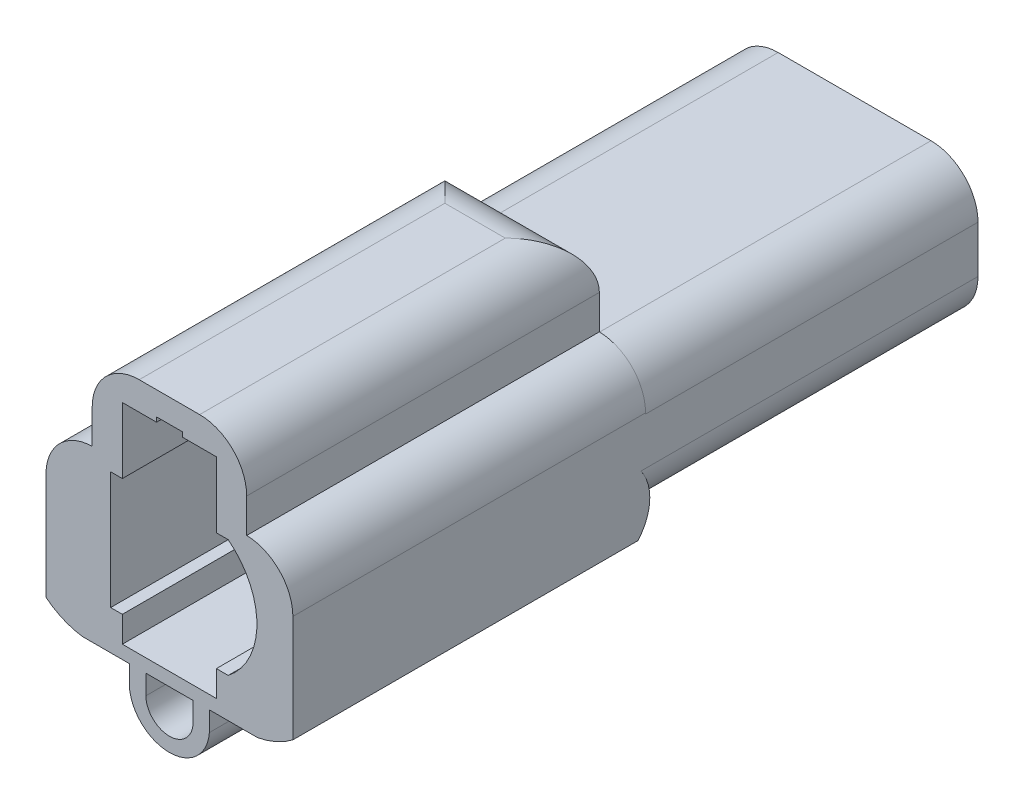
SolidWorks part; units mm, degrees
ref_plane "Front Plane" through (0, 0, 0) normal (0, 0, 1) x (1, 0, 0)
ref_plane "Top Plane" through (0, 0, 0) normal (0, 1, 0) x (1, 0, 0)
ref_plane "Right Plane" through (0, 0, 0) normal (1, 0, 0) x (0, 0, -1)
sketch "Sketch1" plane through (0, 0, 0) normal (0, 0, 1) x (1, 0, 0)
  line L1 (-5.25, 3) -> (5.25, 3)
  line L2 (-5.25, 3) -> (-5.25, -3)
  line L3 (-5.25, -3) -> (5.25, -3)
  line L4 (5.25, 3) -> (5.25, -3)
  line L5 (-5.25, 3) -> (5.25, -3) construction
  line L6 (-5.25, -3) -> (5.25, 3) construction
  point P0 (0, 0)
  dimension "D1" = 10.5
  dimension "D2" = 6
extrude "Boss-Extrude1" add sketch "Sketch1" along normal blind 7.07
sketch "Sketch3" plane through (0, 0, 7.07) normal (0, 0, 1) x (1, 0, 0)
  line L1 (-4.3, 0.9) -> (4.3, 0.9)
  line L2 (-4.3, 0.9) -> (-4.3, -0.9)
  line L3 (-4.3, -0.9) -> (4.3, -0.9)
  line L4 (4.3, 0.9) -> (4.3, -0.9)
  line L5 (-4.3, 0.9) -> (4.3, -0.9) construction
  line L6 (-4.3, -0.9) -> (4.3, 0.9) construction
  point P0 (0, 0)
  dimension "D1" = 8.6
  dimension "D2" = 1.8
extrude "Cut-Extrude2" cut sketch "Sketch3" against normal blind 17
sketch "Sketch4" plane through (0, 0, 7.07) normal (0, 0, 1) x (1, 0, 0)
  line L1 (-5.25, 3) -> (5.25, 3)
  line L2 (-5.25, 3) -> (-5.25, -3)
  line L3 (-5.25, -3) -> (5.25, -3)
  line L4 (5.25, 3) -> (5.25, -3)
  line L5 (-5.25, 3) -> (5.25, -3) construction
  line L6 (-5.25, -3) -> (5.25, 3) construction
  point P0 (0, 0)
extrude "Boss-Extrude2" add sketch "Sketch4" along normal blind 7.07
sketch "Sketch5" plane through (0, 0, 14.14) normal (0, 0, 1) x (1, 0, 0)
  line L1 (-2, 0.9) -> (2, 0.9)
  line L2 (-2, 0.9) -> (-2, -0.9)
  line L3 (-2, -0.9) -> (2, -0.9)
  line L4 (2, 0.9) -> (2, -0.9)
  line L5 (-2, 0.9) -> (2, -0.9) construction
  line L6 (-2, -0.9) -> (2, 0.9) construction
  point P0 (0, 0)
  dimension "D1" = 1.8
  dimension "D2" = 4
extrude "Cut-Extrude3" cut sketch "Sketch5" against normal mid plane 38
fillet "Fillet1" radius 12 1 edges at (2, 0, 7.07)
fillet "Fillet2" radius 12 1 edges at (-2, 0, 7.07)
sketch "Sketch19" plane through (0, 0, 14.14) normal (0, 0, 1) x (1, 0, 0)
  line L1 (-5.25, 5.5) -> (5.25, 5.5)
  line L2 (-5.25, 5.5) -> (-5.25, -5.5)
  line L3 (-5.25, -5.5) -> (5.25, -5.5)
  line L4 (5.25, 5.5) -> (5.25, -5.5)
  line L5 (-5.25, 5.5) -> (5.25, -5.5) construction
  line L6 (-5.25, -5.5) -> (5.25, 5.5) construction
  line L7 (2, 0.9) -> (-2, 0.9)
  line L8 (2, 0.9) -> (2, -0.9)
  line L9 (2, -0.9) -> (-2, -0.9)
  line L10 (-2, 0.9) -> (-2, -0.9)
  line L11 (2, 0.9) -> (-2, -0.9) construction
  line L12 (2, -0.9) -> (-2, 0.9) construction
  point P0 (0, 0)
  point P6 (0, 0)
  dimension "D1" = 11
  dimension "D2" = 10.5
extrude "Boss-Extrude8" add sketch "Sketch19" along normal blind 15
sketch "Sketch20" plane through (0, 0, 29.14) normal (0, 0, 1) x (1, 0, 0)
  line L0 (0, -3.6017) -> (0, -5.5)
  line L1 (-5.25, -5.5) -> (5.25, -5.5) construction
  line L2 (0, -5.5) -> (0, -3.6017)
  line L3 (1.9962, 3.6017) -> (1.9962, 5.3017)
  line L4 (1.9962, -2.5) -> (2.5, -2.5)
  line L5 (-2.5, 2.5) -> (-2.0023, 2.5)
  line L6 (-2.5, 2.5) -> (-2.5, -2.5)
  line L7 (-2.5, -2.5) -> (-2.0023, -2.5)
  line L9 (-2.0023, 2.5) -> (-2.0023, 5.3017)
  line L10 (-2.0023, 5.3017) -> (-0.55, 5.3017)
  line L11 (1.9962, 5.3017) -> (1.9962, 2.5)
  line L12 (0, -3.6017) -> (1.9962, -3.6017)
  line L13 (1.9962, -3.6017) -> (1.9962, -2.5)
  line L15 (-2.0023, -2.5) -> (-2.0023, -3.6017)
  line L16 (-2.0023, -3.6017) -> (0, -3.6017)
  line L18 (1.9962, 3.6017) -> (1.9962, 2.5)
  line L22 (1.9962, 2.5) -> (2.5, 2.5)
  line L23 (5.25, 5.5) -> (-5.25, 5.5) construction
  line L24 (0.55, 5.3017) -> (0.55, 5.5)
  line L25 (-0.55, 5.3017) -> (-0.55, 5.5)
  line L27 (-0.55, 5.5) -> (0.55, 5.5)
  line L28 (0.55, 5.3017) -> (1.9962, 5.3017)
  arc A0 (2.5, 2.5) -> (2.5, -2.5) centre (0.55, 0) cw
  dimension "D1" = 5
  dimension "D2" = 5
extrude "Cut-Extrude8" cut sketch "Sketch20" against normal blind 14.5
sketch "Sketch21" plane through (0, 5.5, 0) normal (0, 1, 0) x (1, 0, 0)
  line L0 (-5.25, -14.14) -> (5.25, -14.14)
  line L1 (5.25, -14.14) -> (5.25, -29.14)
  line L2 (5.25, -29.14) -> (-5.25, -29.14)
  line L3 (-5.25, -29.14) -> (-5.25, -14.14)
extrude "Boss-Extrude9" add sketch "Sketch21" along normal blind 1
sketch "Sketch22" plane through (0, 0, 29.14) normal (0, 0, 1) x (1, 0, 0)
  line L1 (3.2851, 3.0463) -> (5.25, 3.0463)
  line L3 (-5.25, 6.5) -> (-5.25, -5.5) construction
  line L4 (0, 0) -> (0, 2.1098)
  line L5 (0, 2.1098) -> (0, 0)
  line L6 (-1.5897, 0) -> (0, 0)
  line L7 (5.25, 6.5) -> (5.25, 5.5936)
  line L8 (5.25, 6.5) -> (3.7474, 6.5)
  line L11 (-5.25, 5.5936) -> (-5.25, 3.0463)
  line L14 (-5.25, -3.5) -> (-5.25, -5.5)
  line L15 (-3.7014, -4.1682) -> (3.7474, -4.1682)
  line L16 (-5.25, -5.5) -> (5.25, -5.5)
  line L17 (5.25, -5.5) -> (5.25, -3.5)
  line L18 (-5.25, 3.0463) -> (-4.2656, 3.0463)
  line L19 (-4.2656, 3.0463) -> (-3.2851, 3.0463)
  line L20 (-3.2851, 3.0463) -> (-3.2851, 4.0349)
  line L21 (-3.2851, 4.0349) -> (-3.2851, 5.5936)
  line L22 (-3.2851, 5.5936) -> (-3.2851, 6.5)
  line L23 (-5.25, 6.5) -> (5.25, 6.5) construction
  line L24 (-3.2851, 6.5) -> (-5.25, 6.5)
  line L25 (-5.25, 6.5) -> (-5.25, 5.5936)
  line L26 (3.2851, 6.5) -> (3.2851, 3.8366)
  line L27 (3.2851, 3.8366) -> (3.2851, 3.0463)
  line L28 (5.25, -5.5) -> (5.25, 6.5) construction
  line L29 (5.25, 3.0463) -> (5.25, 5.5936)
  line L30 (3.7474, 6.5) -> (3.2851, 6.5)
  arc A4 (-3.7014, -4.1682) -> (-5.25, -3.5) centre (-3.2672, -1.0331) cw
  arc A5 (5.25, -3.5) -> (3.7474, -4.1682) centre (3.1164, -0.7255) cw
extrude "Cut-Extrude10" cut sketch "Sketch22" against normal blind 15
fillet "Fillet6" radius 2 1 edges at (0.023, -4.1682, 14.14)
fillet "Fillet12" radius 2 4 edges at (5.25, -3, 7.07) (-5.25, -3, 7.07) (-5.25, 3, 7.07) (5.25, 3, 7.07)
sketch "Sketch24" plane through (0, 0, 29.14) normal (0, 0, 1) x (1, 0, 0)
  line L1 (-3.7014, -4.1682) -> (3.7474, -4.1682) construction
  line L5 (-1.0042, -4.5) -> (-1.0042, -5.0042)
  line L6 (-1.7065, -4.1682) -> (-1.7065, -5.0042)
  line L12 (1.6996, -4.1682) -> (1.6996, -5.0042)
  line L17 (1.0021, -4.1682) -> (1.0021, -5.0042)
  line L18 (1.0021, -4.1682) -> (1.6996, -4.1682)
  line L21 (-1.0042, -4.5) -> (-1.0042, -4.1682)
  line L22 (-1.0042, -4.1682) -> (-1.7065, -4.1682)
  arc A1 (1.0021, -5.0042) -> (-1.0042, -5.0042) centre (-0.0011, -4.9868) cw
  arc A3 (1.6996, -5.0042) -> (-1.7065, -5.0042) centre (-0.0034, -4.8827) cw
extrude "Boss-Extrude15" add sketch "Sketch24" against normal blind 13
fillet "Fillet15" radius 2 3 edges at (0, 6.5, 14.14) (3.2851, 6.5, 21.64) (-3.2851, 6.5, 21.64)
fillet "Fillet16" radius 2 1 edges at (5.25, 3.0463, 21.64)
fillet "Fillet17" radius 2 1 edges at (-5.25, 3.0463, 21.64)
sketch "Sketch28" plane through (0, 0, 0) normal (0, 0, -1) x (-1, 0, 0)
  line L0 (0, 0) -> (0, -3)
  line L1 (3.25, -3) -> (-3.25, -3) construction
  line L2 (0, -3) -> (3.25, -3)
  line L3 (3.25, -3) -> (-3.25, -3)
  line L4 (0, -3) -> (0.0011, -5.9901)
  line L5 (-1.0049, -3.296) -> (-1.0049, -3.8002)
  line L6 (-1.7072, -2.9641) -> (-1.7072, -3.8002)
  line L7 (1.6989, -2.9641) -> (1.6989, -3.8002)
  line L8 (1.0014, -2.9641) -> (1.0014, -3.8002)
  line L9 (1.0014, -2.9641) -> (1.6989, -2.9641)
  line L10 (-1.0049, -3.296) -> (-1.0049, -2.9641)
  line L11 (-1.0049, -2.9641) -> (-1.7072, -2.9641)
  arc A0 (-1.0021, -5.0042) -> (1.0042, -5.0042) centre (0.0011, -4.9868) ccw construction
  arc A1 (1.0014, -3.8002) -> (-1.0049, -3.8002) centre (-0.0018, -3.7828) cw
  arc A2 (1.6989, -3.8002) -> (-1.7072, -3.8002) centre (-0.0041, -3.6787) cw
